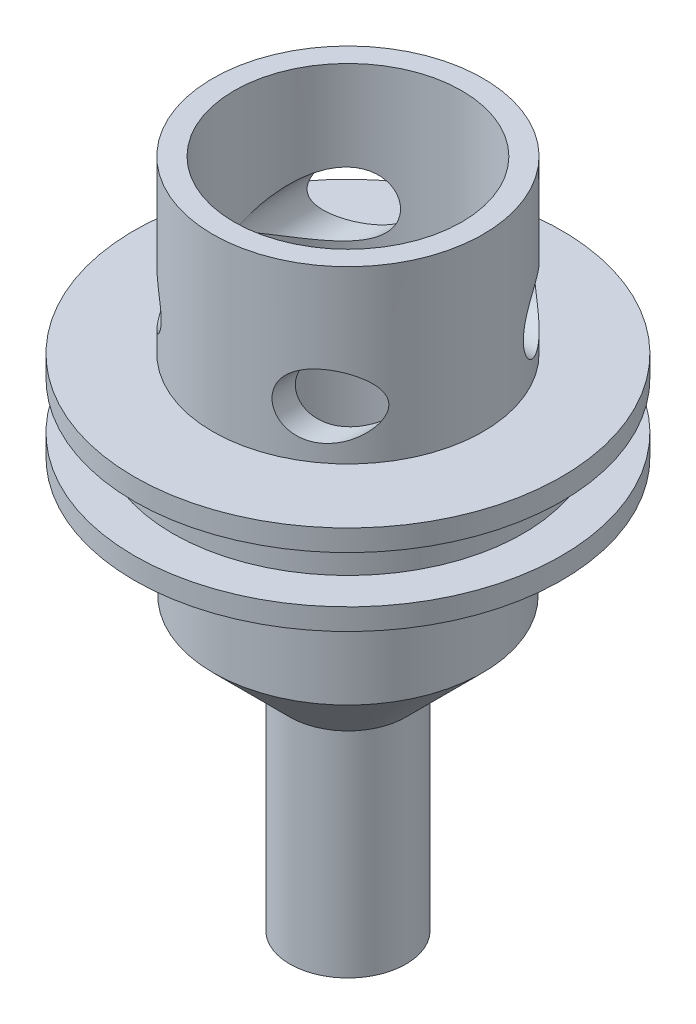
SolidWorks part; units mm, degrees
ref_plane "Front Plane" through (0, 0, 0) normal (0, 0, 1) x (1, 0, 0)
ref_plane "Top Plane" through (0, 0, 0) normal (0, 1, 0) x (1, 0, 0)
ref_plane "Right Plane" through (0, 0, 0) normal (1, 0, 0) x (0, 0, -1)
ref_axis "Centerline" through (0, 55, 0) along (0, -1, 0)
sketch "Sketch2" plane through (0, 0, 0) normal (0, 1, 0) x (1, 0, 0)
  circle A0 centre (0, 0) radius 12.7
  dimension "D1" = 25.4
extrude "Solid Cylinder" add sketch "Sketch2" along normal blind 39.878
sketch "Sketch3" plane through (0, 39.878, 0) normal (0, 1, 0) x (1, 0, 0)
  circle A0 centre (0, 0) radius 1.7272
  dimension "D1" = 3.4544
extrude "All Through Hole" cut sketch "Sketch3" against normal up to next
sketch "Sketch4" plane through (0, 39.878, 0) normal (0, 1, 0) x (1, 0, 0)
  circle A0 centre (0, 0) radius 6.7691
  dimension "D1" = 13.5382
extrude "Swirl Chamber" cut sketch "Sketch4" against normal blind 19.05
sketch "Sketch5" plane through (0, 39.878, 0) normal (0, 1, 0) x (1, 0, 0)
  circle A0 centre (0, 0) radius 8.0391
  circle A1 centre (0, 0) radius 12.7
  dimension "D1" = 25.4
  dimension "D2" = 16.0782
extrude "Top Outer cut" cut sketch "Sketch5" against normal blind 10.16
sketch "Sketch8" plane through (0, 0, 0) normal (0, 0, 1) x (1, 0, 0)
  line L0 (12.7, 0) -> (12.7, 29.718) construction
  line L1 (12.7, 28.448) -> (10.414, 28.448)
  line L2 (12.7, 28.448) -> (12.7, 25.654)
  line L3 (12.7, 25.654) -> (10.414, 25.654)
  line L4 (10.414, 28.448) -> (10.414, 25.654)
  line L5 (12.7, 29.718) -> (-12.7, 29.718) construction
  dimension "D1" = 2.794
  dimension "D2" = 2.286
  dimension "D3" = 1.27
revolve "O Ring Cut" cut sketch "Sketch8" angle 360 about axis through (0, 55, 0) along (0, -1, 0)
sketch "Sketch9" plane through (0, 0, 0) normal (0, 0, 1) x (1, 0, 0)
  line L0 (12.7, 25.654) -> (-12.7, 25.654) construction
  line L1 (12.7, 0) -> (8.001, 0)
  line L2 (12.7, 0) -> (12.7, 24.384)
  line L3 (12.7, 24.384) -> (8.001, 24.384)
  line L4 (8.001, 0) -> (8.001, 24.384)
  dimension "D1" = 4.699
  dimension "D2" = 1.27
revolve "Base Support" cut sketch "Sketch9" angle 360 about axis through (0, 55, 0) along (0, -1, 0)
chamfer "Inner Chamfer" distance 5.08 angle 45 1 edges at (0, 20.828, 1.7272)
sketch "Sketch12" plane through (0, 0, 0) normal (0, 0, 1) x (1, 0, 0)
  line L0 (0, 42.2148) -> (0, -6.3792) construction
  line L1 (6.7691, 42.2148) -> (6.7691, -6.3792) construction
  line L2 (8.0391, 39.878) -> (-8.0391, 39.878) construction
  circle A0 centre (4.8641, 32.639) radius 1.905
  dimension "D1" = 3.81
  dimension "D3" = 7.239
  dimension "D2" = 6.7691
extrude "Inlet Hole" cut sketch "Sketch12" along normal up to next
pattern_circular "Inlet Hole Pattern" count 4 over 360 about axis through (0, 55, 0) along (0, -1, 0) of "Inlet Hole"
sketch "Sketch13" plane through (0, 0, 0) normal (0, 0, 1) x (1, 0, 0)
  line L0 (-8.001, 17.272) -> (-3.4544, 12.7254)
  line L1 (-8.001, 24.384) -> (-8.001, 0) construction
  line L2 (-3.4544, 12.7254) -> (-3.4544, 0)
  line L3 (-3.4544, 0) -> (-8.001, 0)
  line L4 (-8.001, 0) -> (-8.001, 17.272)
  line L5 (-8.001, 0) -> (8.001, 0) construction
  line L7 (0, 46.5908) -> (0, -8.5124) construction
  dimension "D1" = 45
  dimension "D2" = 7.112
  dimension "D3" = 3.4544
revolve "Outer Chamfer and Stem" cut sketch "Sketch13" angle 360 about L7
